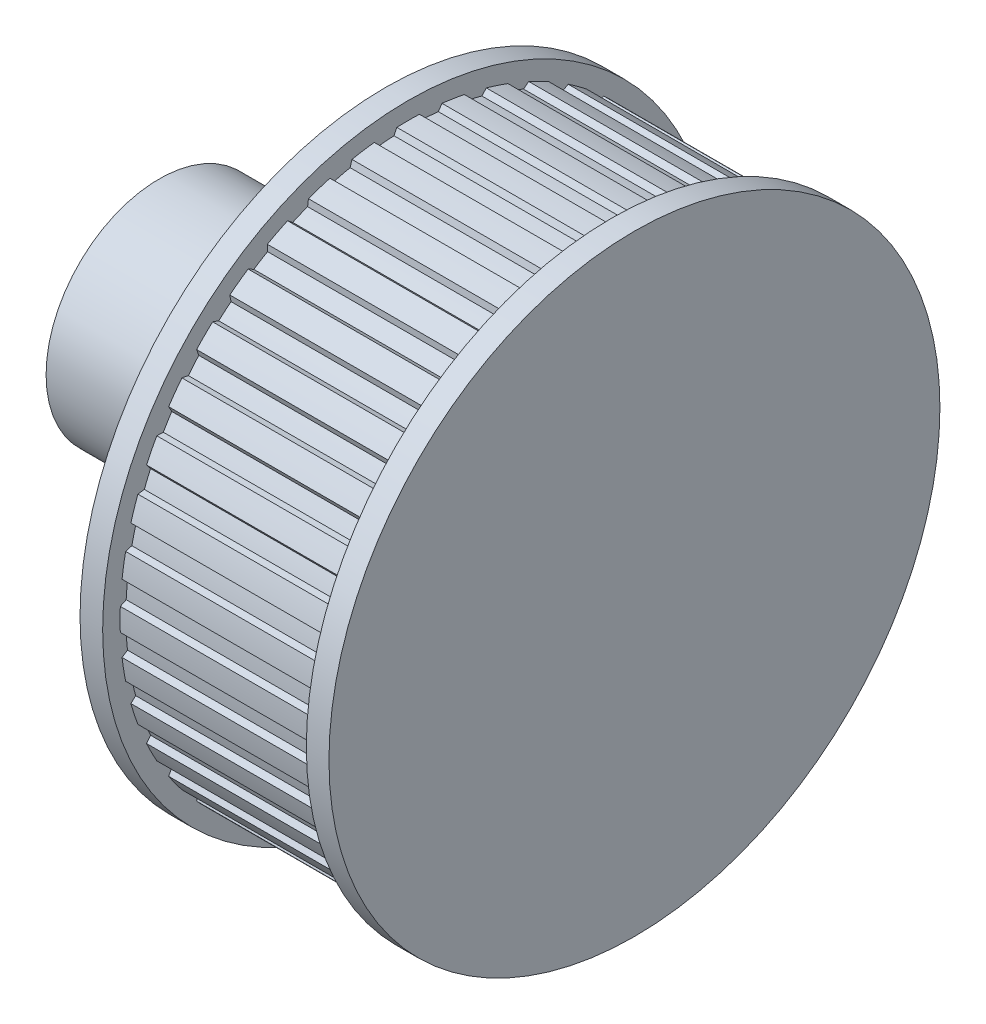
SolidWorks part; units mm, degrees
ref_plane "Front Plane" through (0, 0, 0) normal (0, 0, 1) x (1, 0, 0)
ref_plane "Top Plane" through (0, 0, 0) normal (0, 1, 0) x (1, 0, 0)
ref_plane "Right Plane" through (0, 0, 0) normal (1, 0, 0) x (0, 0, -1)
ref_plane "Plane4" through (0, 0, 0) normal (0, 0, -1) x (-1, 0, 0)
sketch "Sketch5" plane through (0, 0, 0) normal (1, 0, 0) x (0, 0, -1)
  line L1 (0, 12.73) -> (0, 0) construction
  line L2 (-0.6228, 12.4594) -> (-0.4998, 12.7202)
  line L3 (0.4998, 12.7202) -> (0.6228, 12.4594)
  line L4 (1.3339, 12.4035) -> (1.4963, 12.6418)
  line L5 (2.4835, 12.4854) -> (2.5642, 12.2086)
  line L6 (3.2578, 12.0421) -> (3.4554, 12.2521)
  line L7 (4.4061, 11.9432) -> (4.4425, 11.6572)
  line L8 (5.1015, 11.3842) -> (5.3295, 11.5607)
  line L9 (6.2201, 11.1069) -> (6.2114, 10.8187)
  line L10 (6.8196, 10.446) -> (7.0724, 10.5846)
  line L11 (7.8811, 9.9971) -> (7.8273, 9.7138)
  line L12 (8.3698, 9.2506) -> (8.6411, 9.3479)
  line L13 (9.3479, 8.6411) -> (9.2506, 8.3698)
  line L14 (9.7138, 7.8273) -> (9.9971, 7.8811)
  line L15 (10.5846, 7.0724) -> (10.446, 6.8196)
  line L16 (10.8187, 6.2114) -> (11.1069, 6.2201)
  line L17 (11.5607, 5.3295) -> (11.3842, 5.1015)
  line L18 (11.6572, 4.4425) -> (11.9432, 4.4061)
  line L19 (12.2521, 3.4554) -> (12.0421, 3.2578)
  line L20 (12.2086, 2.5642) -> (12.4854, 2.4835)
  line L21 (12.6418, 1.4963) -> (12.4035, 1.3339)
  line L22 (12.4594, 0.6228) -> (12.7202, 0.4998)
  line L23 (12.7202, -0.4998) -> (12.4594, -0.6228)
  line L24 (12.4035, -1.3339) -> (12.6418, -1.4963)
  line L25 (12.4854, -2.4835) -> (12.2086, -2.5642)
  line L26 (12.0421, -3.2578) -> (12.2521, -3.4554)
  line L27 (11.9432, -4.4061) -> (11.6572, -4.4425)
  line L28 (11.3842, -5.1015) -> (11.5607, -5.3295)
  line L29 (11.1069, -6.2201) -> (10.8187, -6.2114)
  line L30 (10.446, -6.8196) -> (10.5846, -7.0724)
  line L31 (9.9971, -7.8811) -> (9.7138, -7.8273)
  line L32 (9.2506, -8.3698) -> (9.3479, -8.6411)
  line L33 (8.6411, -9.3479) -> (8.3698, -9.2506)
  line L34 (7.8273, -9.7138) -> (7.8811, -9.9971)
  line L35 (7.0724, -10.5846) -> (6.8196, -10.446)
  line L36 (6.2114, -10.8187) -> (6.2201, -11.1069)
  line L37 (5.3295, -11.5607) -> (5.1015, -11.3842)
  line L38 (4.4425, -11.6572) -> (4.4061, -11.9432)
  line L39 (3.4554, -12.2521) -> (3.2578, -12.0421)
  line L40 (2.5642, -12.2086) -> (2.4835, -12.4854)
  line L41 (1.4963, -12.6418) -> (1.3339, -12.4035)
  line L42 (0.6228, -12.4594) -> (0.4998, -12.7202)
  line L43 (-0.4998, -12.7202) -> (-0.6228, -12.4594)
  line L44 (-1.3339, -12.4035) -> (-1.4963, -12.6418)
  line L45 (-2.4835, -12.4854) -> (-2.5642, -12.2086)
  line L46 (-3.2578, -12.0421) -> (-3.4554, -12.2521)
  line L47 (-4.4061, -11.9432) -> (-4.4425, -11.6572)
  line L48 (-5.1015, -11.3842) -> (-5.3295, -11.5607)
  line L49 (-6.2201, -11.1069) -> (-6.2114, -10.8187)
  line L50 (-6.8196, -10.446) -> (-7.0724, -10.5846)
  line L51 (-7.8811, -9.9971) -> (-7.8273, -9.7138)
  line L52 (-8.3698, -9.2506) -> (-8.6411, -9.3479)
  line L53 (-9.3479, -8.6411) -> (-9.2506, -8.3698)
  line L54 (-9.7138, -7.8273) -> (-9.9971, -7.8811)
  line L55 (-10.5846, -7.0724) -> (-10.446, -6.8196)
  line L56 (-10.8187, -6.2114) -> (-11.1069, -6.2201)
  line L57 (-11.5607, -5.3295) -> (-11.3842, -5.1015)
  line L58 (-11.6572, -4.4425) -> (-11.9432, -4.4061)
  line L59 (-12.2521, -3.4554) -> (-12.0421, -3.2578)
  line L60 (-12.2086, -2.5642) -> (-12.4854, -2.4835)
  line L61 (-12.6418, -1.4963) -> (-12.4035, -1.3339)
  line L62 (-12.4594, -0.6228) -> (-12.7202, -0.4998)
  line L63 (-12.7202, 0.4998) -> (-12.4594, 0.6228)
  line L64 (-12.4035, 1.3339) -> (-12.6418, 1.4963)
  line L65 (-12.4854, 2.4835) -> (-12.2086, 2.5642)
  line L66 (-12.0421, 3.2578) -> (-12.2521, 3.4554)
  line L67 (-11.9432, 4.4061) -> (-11.6572, 4.4425)
  line L68 (-11.3842, 5.1015) -> (-11.5607, 5.3295)
  line L69 (-11.1069, 6.2201) -> (-10.8187, 6.2114)
  line L70 (-10.446, 6.8196) -> (-10.5846, 7.0724)
  line L71 (-9.9971, 7.8811) -> (-9.7138, 7.8273)
  line L72 (-9.2506, 8.3698) -> (-9.3479, 8.6411)
  line L73 (-8.6411, 9.3479) -> (-8.3698, 9.2506)
  line L74 (-7.8273, 9.7138) -> (-7.8811, 9.9971)
  line L75 (-7.0724, 10.5846) -> (-6.8196, 10.446)
  line L76 (-6.2114, 10.8187) -> (-6.2201, 11.1069)
  line L77 (-5.3295, 11.5607) -> (-5.1015, 11.3842)
  line L78 (-4.4425, 11.6572) -> (-4.4061, 11.9432)
  line L79 (-3.4554, 12.2521) -> (-3.2578, 12.0421)
  line L80 (-2.5642, 12.2086) -> (-2.4835, 12.4854)
  line L81 (-1.4963, 12.6418) -> (-1.3339, 12.4035)
  arc A4 (1.3339, 12.4035) -> (0.6228, 12.4594) centre (0, 0) ccw
  arc A6 (0.4998, 12.7202) -> (-0.4998, 12.7202) centre (0, 0) ccw
  arc A7 (2.4835, 12.4854) -> (1.4963, 12.6418) centre (0, 0) ccw
  arc A8 (3.2578, 12.0421) -> (2.5642, 12.2086) centre (0, 0) ccw
  arc A9 (4.4061, 11.9432) -> (3.4554, 12.2521) centre (0, 0) ccw
  arc A10 (5.1015, 11.3842) -> (4.4425, 11.6572) centre (0, 0) ccw
  arc A11 (6.2201, 11.1069) -> (5.3295, 11.5607) centre (0, 0) ccw
  arc A12 (6.8196, 10.446) -> (6.2114, 10.8187) centre (0, 0) ccw
  arc A13 (7.8811, 9.9971) -> (7.0724, 10.5846) centre (0, 0) ccw
  arc A14 (8.3698, 9.2506) -> (7.8273, 9.7138) centre (0, 0) ccw
  arc A15 (9.3479, 8.6411) -> (8.6411, 9.3479) centre (0, 0) ccw
  arc A16 (9.7138, 7.8273) -> (9.2506, 8.3698) centre (0, 0) ccw
  arc A17 (10.5846, 7.0724) -> (9.9971, 7.8811) centre (0, 0) ccw
  arc A18 (10.8187, 6.2114) -> (10.446, 6.8196) centre (0, 0) ccw
  arc A19 (11.5607, 5.3295) -> (11.1069, 6.2201) centre (0, 0) ccw
  arc A20 (11.6572, 4.4425) -> (11.3842, 5.1015) centre (0, 0) ccw
  arc A21 (12.2521, 3.4554) -> (11.9432, 4.4061) centre (0, 0) ccw
  arc A22 (12.2086, 2.5642) -> (12.0421, 3.2578) centre (0, 0) ccw
  arc A23 (12.6418, 1.4963) -> (12.4854, 2.4835) centre (0, 0) ccw
  arc A24 (12.4594, 0.6228) -> (12.4035, 1.3339) centre (0, 0) ccw
  arc A25 (12.7202, -0.4998) -> (12.7202, 0.4998) centre (0, 0) ccw
  arc A26 (12.4035, -1.3339) -> (12.4594, -0.6228) centre (0, 0) ccw
  arc A27 (12.4854, -2.4835) -> (12.6418, -1.4963) centre (0, 0) ccw
  arc A28 (12.0421, -3.2578) -> (12.2086, -2.5642) centre (0, 0) ccw
  arc A29 (11.9432, -4.4061) -> (12.2521, -3.4554) centre (0, 0) ccw
  arc A30 (11.3842, -5.1015) -> (11.6572, -4.4425) centre (0, 0) ccw
  arc A31 (11.1069, -6.2201) -> (11.5607, -5.3295) centre (0, 0) ccw
  arc A32 (10.446, -6.8196) -> (10.8187, -6.2114) centre (0, 0) ccw
  arc A33 (9.9971, -7.8811) -> (10.5846, -7.0724) centre (0, 0) ccw
  arc A34 (9.2506, -8.3698) -> (9.7138, -7.8273) centre (0, 0) ccw
  arc A35 (8.6411, -9.3479) -> (9.3479, -8.6411) centre (0, 0) ccw
  arc A36 (7.8273, -9.7138) -> (8.3698, -9.2506) centre (0, 0) ccw
  arc A37 (7.0724, -10.5846) -> (7.8811, -9.9971) centre (0, 0) ccw
  arc A38 (6.2114, -10.8187) -> (6.8196, -10.446) centre (0, 0) ccw
  arc A39 (5.3295, -11.5607) -> (6.2201, -11.1069) centre (0, 0) ccw
  arc A40 (4.4425, -11.6572) -> (5.1015, -11.3842) centre (0, 0) ccw
  arc A41 (3.4554, -12.2521) -> (4.4061, -11.9432) centre (0, 0) ccw
  arc A42 (2.5642, -12.2086) -> (3.2578, -12.0421) centre (0, 0) ccw
  arc A43 (1.4963, -12.6418) -> (2.4835, -12.4854) centre (0, 0) ccw
  arc A44 (0.6228, -12.4594) -> (1.3339, -12.4035) centre (0, 0) ccw
  arc A45 (-0.4998, -12.7202) -> (0.4998, -12.7202) centre (0, 0) ccw
  arc A46 (-1.3339, -12.4035) -> (-0.6228, -12.4594) centre (0, 0) ccw
  arc A47 (-2.4835, -12.4854) -> (-1.4963, -12.6418) centre (0, 0) ccw
  arc A48 (-3.2578, -12.0421) -> (-2.5642, -12.2086) centre (0, 0) ccw
  arc A49 (-4.4061, -11.9432) -> (-3.4554, -12.2521) centre (0, 0) ccw
  arc A50 (-5.1015, -11.3842) -> (-4.4425, -11.6572) centre (0, 0) ccw
  arc A51 (-6.2201, -11.1069) -> (-5.3295, -11.5607) centre (0, 0) ccw
  arc A52 (-6.8196, -10.446) -> (-6.2114, -10.8187) centre (0, 0) ccw
  arc A53 (-7.8811, -9.9971) -> (-7.0724, -10.5846) centre (0, 0) ccw
  arc A54 (-8.3698, -9.2506) -> (-7.8273, -9.7138) centre (0, 0) ccw
  arc A55 (-9.3479, -8.6411) -> (-8.6411, -9.3479) centre (0, 0) ccw
  arc A56 (-9.7138, -7.8273) -> (-9.2506, -8.3698) centre (0, 0) ccw
  arc A57 (-10.5846, -7.0724) -> (-9.9971, -7.8811) centre (0, 0) ccw
  arc A58 (-10.8187, -6.2114) -> (-10.446, -6.8196) centre (0, 0) ccw
  arc A59 (-11.5607, -5.3295) -> (-11.1069, -6.2201) centre (0, 0) ccw
  arc A60 (-11.6572, -4.4425) -> (-11.3842, -5.1015) centre (0, 0) ccw
  arc A61 (-12.2521, -3.4554) -> (-11.9432, -4.4061) centre (0, 0) ccw
  arc A62 (-12.2086, -2.5642) -> (-12.0421, -3.2578) centre (0, 0) ccw
  arc A63 (-12.6418, -1.4963) -> (-12.4854, -2.4835) centre (0, 0) ccw
  arc A64 (-12.4594, -0.6228) -> (-12.4035, -1.3339) centre (0, 0) ccw
  arc A65 (-12.7202, 0.4998) -> (-12.7202, -0.4998) centre (0, 0) ccw
  arc A66 (-12.4035, 1.3339) -> (-12.4594, 0.6228) centre (0, 0) ccw
  arc A67 (-12.4854, 2.4835) -> (-12.6418, 1.4963) centre (0, 0) ccw
  arc A68 (-12.0421, 3.2578) -> (-12.2086, 2.5642) centre (0, 0) ccw
  arc A69 (-11.9432, 4.4061) -> (-12.2521, 3.4554) centre (0, 0) ccw
  arc A70 (-11.3842, 5.1015) -> (-11.6572, 4.4425) centre (0, 0) ccw
  arc A71 (-11.1069, 6.2201) -> (-11.5607, 5.3295) centre (0, 0) ccw
  arc A72 (-10.446, 6.8196) -> (-10.8187, 6.2114) centre (0, 0) ccw
  arc A73 (-9.9971, 7.8811) -> (-10.5846, 7.0724) centre (0, 0) ccw
  arc A74 (-9.2506, 8.3698) -> (-9.7138, 7.8273) centre (0, 0) ccw
  arc A75 (-8.6411, 9.3479) -> (-9.3479, 8.6411) centre (0, 0) ccw
  arc A76 (-7.8273, 9.7138) -> (-8.3698, 9.2506) centre (0, 0) ccw
  arc A77 (-7.0724, 10.5846) -> (-7.8811, 9.9971) centre (0, 0) ccw
  arc A78 (-6.2114, 10.8187) -> (-6.8196, 10.446) centre (0, 0) ccw
  arc A79 (-5.3295, 11.5607) -> (-6.2201, 11.1069) centre (0, 0) ccw
  arc A80 (-4.4425, 11.6572) -> (-5.1015, 11.3842) centre (0, 0) ccw
  arc A81 (-3.4554, 12.2521) -> (-4.4061, 11.9432) centre (0, 0) ccw
  arc A82 (-2.5642, 12.2086) -> (-3.2578, 12.0421) centre (0, 0) ccw
  arc A83 (-1.4963, 12.6418) -> (-2.4835, 12.4854) centre (0, 0) ccw
  arc A84 (-0.6228, 12.4594) -> (-1.3339, 12.4035) centre (0, 0) ccw
  point P204 (0, 0)
  dimension "D2" = 12.73
  dimension "D4" = 12.475
  dimension "D3" = 0.4998
  dimension "D5" = 0.6228
  dimension "D1" = 40
extrude "Boss-Extrude1" add sketch "Sketch5" along normal blind 9
sketch "Sketch6" plane through (9, 0, 0) normal (1, 0, 0) x (0, 0, -1)
  circle A0 centre (0, 0) radius 13.5
  dimension "D1" = 27
extrude "Boss-Extrude2" add sketch "Sketch6" along normal blind 1
extrude "Boss-Extrude3" add sketch "Sketch6<3>" against normal blind 1 from surface starting at face at (0, 0, 0)
sketch "Sketch6<3>" plane through (9, 0, 0) normal (1, 0, 0) x (0, 0, -1) same geometry as "Sketch6"
sketch "Sketch7" plane through (-1, 0, 0) normal (-1, 0, 0) x (0, 0, 1)
  circle A0 centre (0, 0) radius 5
  dimension "D1" = 10
extrude "Boss-Extrude4" add sketch "Sketch7" along normal blind 10
ref_plane "Plane5" through (0, 5, 0) normal (0, 1, 0) x (1, 0, 0)
ref_plane "Plane6" through (0, 0, 5) normal (0, 0, 1) x (1, 0, 0)
sketch "Sketch8" plane through (-11, 0, 0) normal (-1, 0, 0) x (0, 0, 1)
  circle A0 centre (0, 0) radius 3
  dimension "D1" = 6
extrude "Cut-Extrude1" cut sketch "Sketch8" against normal blind 10
sketch "Sketch9" plane through (0, 5, 0) normal (0, 1, 0) x (1, 0, 0)
  line L0 (-6, 5) -> (-6, 0) construction
  line L1 (-1, 5) -> (-11, 5) construction
  line L2 (0, 0) -> (-6, 0) construction
  circle A0 centre (-6, 0) radius 1.6
  dimension "D1" = 3.2
extrude "Cut-Extrude2" cut sketch "Sketch9" against normal up to next
